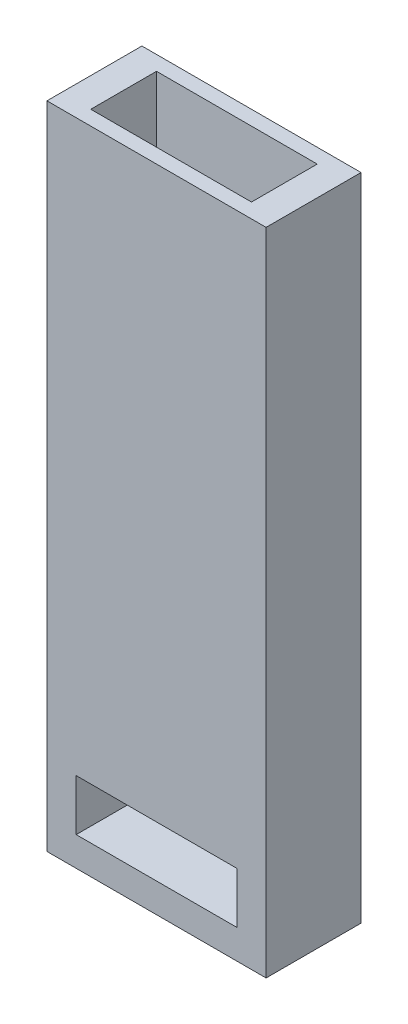
SolidWorks part; units mm, degrees
ref_plane "Front Plane" through (0, 0, 0) normal (0, 0, 1) x (1, 0, 0)
ref_plane "Top Plane" through (0, 0, 0) normal (0, 1, 0) x (1, 0, 0)
ref_plane "Right Plane" through (0, 0, 0) normal (1, 0, 0) x (0, 0, -1)
sketch "Sketch1" plane through (0, 0, 0) normal (0, 1, 0) x (1, 0, 0)
  line L1 (0, 0) -> (30, 0)
  line L2 (0, 0) -> (0, -13)
  line L3 (0, -13) -> (30, -13)
  line L4 (30, 0) -> (30, -13)
  dimension "D1" = 30
  dimension "D2" = 13
extrude "Boss-Extrude1" add sketch "Sketch1" along normal blind 85
sketch "Sketch2" plane through (0, 85, 0) normal (0, 1, 0) x (1, 0, 0)
  line L0 (0, -6.5) -> (30, -6.5) construction
  line L1 (0, 0) -> (0, -13) construction
  line L2 (30, -13) -> (30, 0) construction
  line L4 (4, -11) -> (26, -11)
  line L5 (4, -11) -> (4, -2)
  line L6 (4, -2) -> (26, -2)
  line L7 (26, -11) -> (26, -2)
  line L8 (4, -11) -> (26, -2) construction
  line L9 (4, -2) -> (26, -11) construction
  point P6 (15, -6.5)
  dimension "D1" = 22
  dimension "D2" = 9
extrude "Cut-Extrude2" cut sketch "Sketch2" against normal blind 85
sketch "Sketch5" plane through (0, 0, 0) normal (0, 1, 0) x (1, 0, 0)
  line L1 (0, 0) -> (30, 0)
  line L2 (0, 0) -> (0, -13)
  line L3 (0, -13) -> (30, -13)
  line L4 (30, 0) -> (30, -13)
extrude "Boss-Extrude3" add sketch "Sketch5" against normal blind 4
sketch "Sketch7" plane through (0, 85, 0) normal (0, 1, 0) x (1, 0, 0)
  line L0 (4, -13) -> (4, 0) construction
  line L1 (0, -13) -> (30, -13) construction
  line L2 (30, 0) -> (0, 0) construction
  line L3 (26, -13) -> (26, 0) construction
sketch "Sketch10" plane through (0, 85, 0) normal (0, 1, 0) x (1, 0, 0)
  line L0 (4, -13) -> (0, -13) construction
sketch "Sketch12" plane through (0, 0, 13) normal (0, 0, 1) x (1, 0, 0)
  line L0 (0, -4) -> (0, 0) construction
  line L1 (0, 85) -> (0, -4) construction
  line L2 (0, -4) -> (4, -4) construction
  line L3 (0, -4) -> (30, -4) construction
  line L4 (4, -4) -> (4, 0) construction
  line L5 (4, 0) -> (4, 7) construction
  line L7 (4, 0) -> (26, 0)
  line L8 (4, 0) -> (4, 7)
  line L9 (4, 7) -> (26, 7)
  line L10 (26, 0) -> (26, 7)
  dimension "D1" = 22
extrude "Cut-Extrude4" cut sketch "Sketch12" against normal blind 13 contours L9 L10 L7 L8
